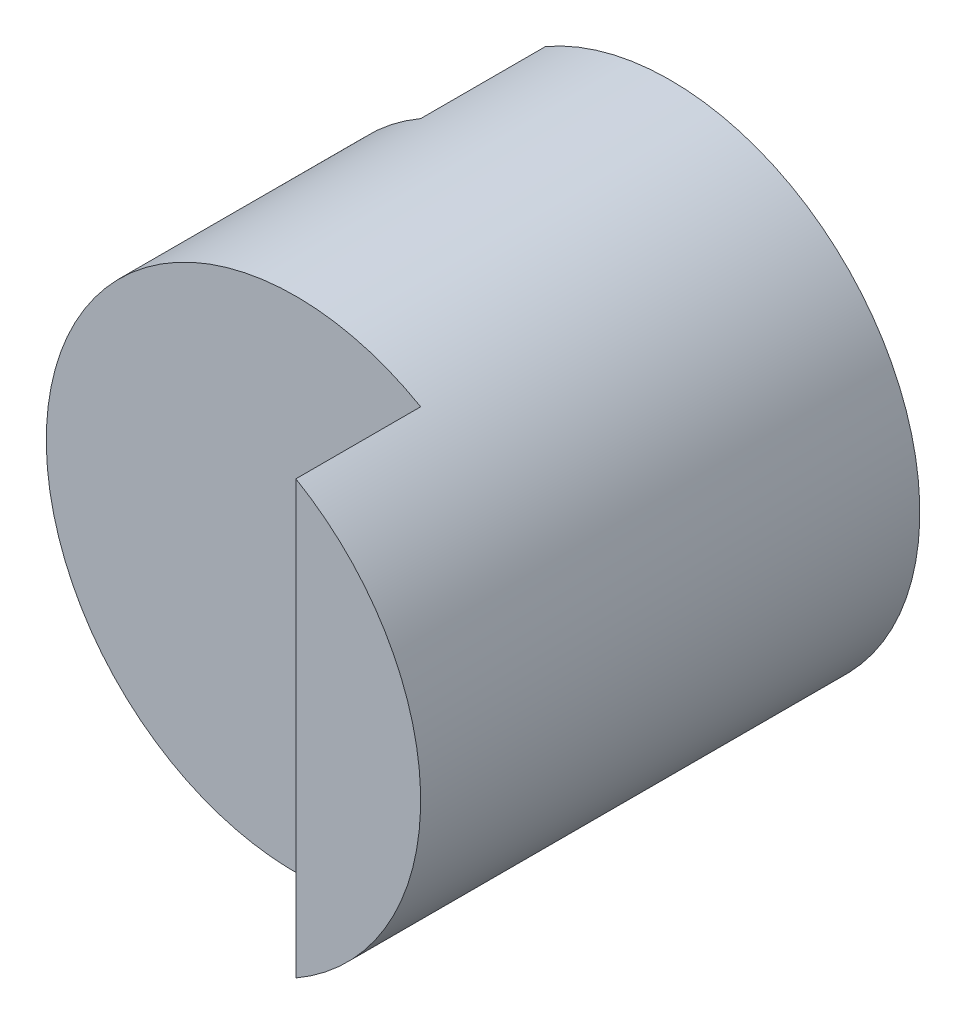
SolidWorks part; units mm, degrees
ref_plane "Front Plane" through (0, 0, 0) normal (0, 0, 1) x (1, 0, 0)
ref_plane "Top Plane" through (0, 0, 0) normal (0, 1, 0) x (1, 0, 0)
ref_plane "Right Plane" through (0, 0, 0) normal (1, 0, 0) x (0, 0, -1)
sketch "Sketch1" plane through (0, 0, 0) normal (0, 0, 1) x (1, 0, 0)
  circle A0 centre (0, 0) radius 20
  dimension "D1" = 40
extrude "Boss-Extrude1" add sketch "Sketch1" along normal blind 40
sketch "Sketch2" plane through (0, 0, 0) normal (0, 1, 0) x (1, 0, 0)
  line L1 (-20, -40) -> (10, -40)
  line L2 (-20, -40) -> (-20, -30)
  line L3 (-20, -30) -> (10, -30)
  line L4 (10, -40) -> (10, -30)
  line L5 (-20, 0) -> (-10, 0)
  line L6 (-20, 0) -> (-20, -10)
  line L7 (-20, -10) -> (-10, -10)
  line L8 (-10, 0) -> (-10, -10)
  dimension "D1" = 10
  dimension "D2" = 10
  dimension "D3" = 30
  dimension "D4" = 10
extrude "Cut-Extrude1" cut sketch "Sketch2" against normal blind 40 and the other way blind 40
